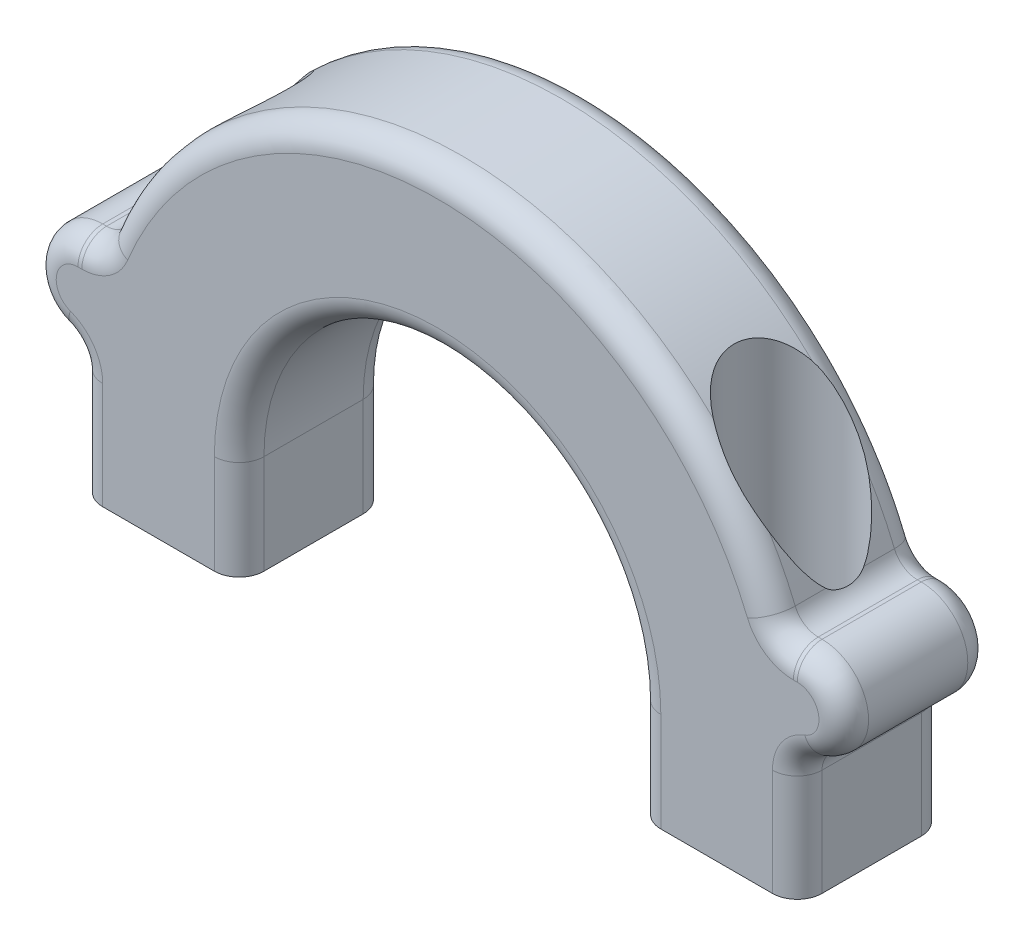
SolidWorks part; units mm, degrees
ref_plane "Plane XZ" through (0, 0, 0) normal (0, 0, 1) x (1, 0, 0)
ref_plane "Plane XY" through (0, 0, 0) normal (0, 1, 0) x (1, 0, 0)
ref_plane "Plane YZ" through (0, 0, 0) normal (1, 0, 0) x (0, 0, -1)
sketch "Sketch1" plane through (0, 0, 0) normal (0, 0, 1) x (1, 0, 0)
  line L0 (-10.16, 0) -> (-10.16, 5.08)
  line L1 (-18.415, 0) -> (18.415, 0) construction
  line L2 (-18.415, 0) -> (-18.415, 5.08)
  line L3 (-18.415, 5.08) -> (18.415, 5.08) construction
  line L4 (18.415, 0) -> (18.415, 5.08)
  line L5 (10.16, 0) -> (10.16, 5.08)
  line L6 (-10.16, 0) -> (-18.415, 0)
  line L7 (10.16, 0) -> (18.415, 0)
  line L8 (0, 0) -> (0, 5.08) construction
  arc A0 (-18.415, 5.08) -> (18.415, 5.08) centre (0, 5.08) cw
  arc A1 (-10.16, 5.08) -> (10.16, 5.08) centre (0, 5.08) cw
  point P6 (-14.2875, 0)
  dimension "D2" = 28.575
  dimension "D3" = 5.08
  dimension "D4" = 20.32
  dimension "D1" = 8.255
extrude "Boss-Extrude1" add sketch "Sketch1" along normal mid plane 7.62
sketch "Sketch5" plane through (0, 0, 3.81) normal (0, 0, 1) x (1, 0, 0)
  line L0 (-18.415, 5.08) -> (-18.415, 0) construction
  line L1 (-18.415, 0) -> (-10.16, 0) construction
  line L2 (-18.415, 6.5087) -> (-18.415, 5.08)
  line L3 (-18.415, 5.08) -> (-15.3293, 5.08)
  line L4 (-15.3293, 5.08) -> (-15.3293, 11.2712)
  line L5 (-18.415, 11.2712) -> (-15.3293, 11.2712)
  circle A0 centre (-18.415, 8.89) radius 2.3813 construction
  arc A1 (-18.415, 6.5087) -> (-18.415, 11.2712) centre (-18.415, 8.89) cw
  dimension "D1" = 4.7625
  dimension "D2" = 8.89
extrude "Boss-Extrude2" add sketch "Sketch5" against normal up to surface (7.62 mm away) up to face at (0, 6.1119, -3.81)
sketch "Sketch3" plane through (0, 0, 0) normal (0, 0, 1) x (1, 0, 0)
  line L0 (-14.2875, 0) -> (-14.2875, 21.4862)
  line L1 (-10.16, 0) -> (-18.415, 0) construction
  line L2 (-14.2875, 21.4862) -> (-17.2085, 21.4862)
  line L3 (-17.2085, 21.4862) -> (-17.2085, 6.35)
  line L4 (-17.2085, 6.35) -> (-15.9385, 6.35)
  line L5 (-15.9385, 6.35) -> (-15.9385, 0)
  line L6 (-15.9385, 0) -> (-14.2875, 0)
  line L7 (-14.2875, 0) -> (-14.2875, -3.2281) construction
  arc A0 (18.415, 5.08) -> (-18.415, 5.08) centre (0, 5.08) ccw construction
  point P10 (-17.2085, 11.6359)
  dimension "D1" = 3.302
  dimension "D2" = 5.842
  dimension "D3" = 5.2859
  dimension "D4" = 6.35
revolve "Cut-Revolve3" cut sketch "Sketch3" angle 360 about L7
mirror "Mirror1" about plane through (0, 0, 0) normal (1, 0, 0) of "Boss-Extrude2", "Cut-Revolve3"
fillet "Fillet2" radius 1.27 4 edges at (18.415, 6.5087, 0) (17.343, 11.2712, 0) (-18.415, 6.5087, 0) (-17.343, 11.2712, 0)
fillet "Fillet1" radius 1.27 28 edges at (18.415, 2.7334, -3.81) (-18.415, 2.7334, -3.81) (18.415, 2.7334, 3.81) (-18.415, 2.7334, 3.81) (10.16, 2.54, -3.81) (0, 15.24, -3.81) (-10.16, 2.54, 3.81) (10.16, 2.54, 3.81) (0, 23.495, -3.81) (0, 23.495, 3.81) (-10.16, 2.54, -3.81) (0, 15.24, 3.81) (18.6424, 6.192, -3.81) (20.7588, 9.3108, -3.81) (18.3156, 11.2712, -3.81) (17.5085, 11.4867, -3.81) (-18.6424, 6.192, -3.81) (-20.7588, 9.3108, -3.81) (-18.3156, 11.2712, -3.81) (-17.5085, 11.4867, -3.81) (18.6424, 6.192, 3.81) (20.7588, 9.3108, 3.81) (18.3156, 11.2712, 3.81) (17.5085, 11.4867, 3.81) (-18.6424, 6.192, 3.81) (-20.7588, 9.3108, 3.81) (-18.3156, 11.2712, 3.81) (-17.5085, 11.4867, 3.81)
